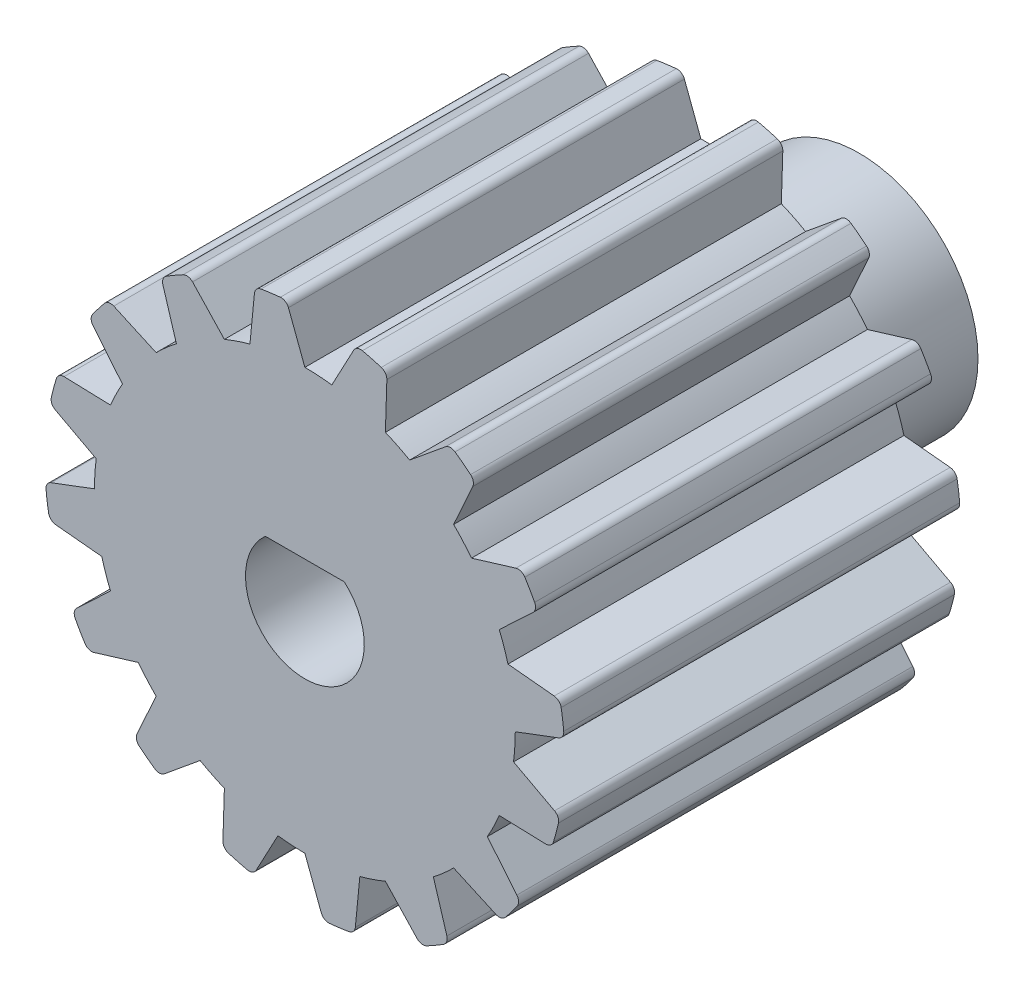
SolidWorks part; units mm, degrees
ref_plane "Alzado" through (0, 0, 0) normal (0, 0, 1) x (1, 0, 0)
ref_plane "Planta" through (0, 0, 0) normal (0, 1, 0) x (1, 0, 0)
ref_plane "Vista lateral" through (0, 0, 0) normal (1, 0, 0) x (0, 0, -1)
sketch "Croquis2" plane through (0, 0, 0) normal (0, 0, 1) x (1, 0, 0)
  line L0 (0, 0) -> (0, 7.9702) construction
  line L2 (-2.0817, 7.6936) -> (-1.9112, 9.4453)
  line L3 (-1.0408, 7.8319) -> (0, 0) construction
  line L4 (0, 7.9702) -> (-0.6221, 9.6166)
  line L5 (1.021, 7.9046) -> (1.8489, 9.4577)
  line L6 (3.0501, 7.3635) -> (3.1053, 9.1227)
  line L7 (3.9682, 6.9122) -> (5.3274, 8.0302)
  line L8 (5.6358, 5.6358) -> (6.3601, 7.2399)
  line L9 (6.3113, 4.8674) -> (7.9949, 5.3803)
  line L10 (7.3635, 3.0501) -> (8.6465, 4.2549)
  line L11 (7.6936, 2.0817) -> (9.4453, 1.9112)
  line L12 (7.9702, 0) -> (9.6166, 0.6221)
  line L13 (7.9046, -1.021) -> (9.4577, -1.8489)
  line L14 (7.3635, -3.0501) -> (9.1227, -3.1053)
  line L15 (6.9122, -3.9682) -> (8.0302, -5.3274)
  line L16 (5.6358, -5.6358) -> (7.2399, -6.3601)
  line L17 (4.8674, -6.3113) -> (5.3803, -7.9949)
  line L18 (3.0501, -7.3635) -> (4.2549, -8.6465)
  line L19 (2.0817, -7.6936) -> (1.9112, -9.4453)
  line L20 (0, -7.9702) -> (0.6221, -9.6166)
  line L21 (-1.021, -7.9046) -> (-1.8489, -9.4577)
  line L22 (-3.0501, -7.3635) -> (-3.1053, -9.1227)
  line L23 (-3.9682, -6.9122) -> (-5.3274, -8.0302)
  line L24 (-5.6358, -5.6358) -> (-6.3601, -7.2399)
  line L25 (-6.3113, -4.8674) -> (-7.9949, -5.3803)
  line L26 (-7.3635, -3.0501) -> (-8.6465, -4.2549)
  line L27 (-7.6936, -2.0817) -> (-9.4453, -1.9112)
  line L28 (-7.9702, 0) -> (-9.6166, -0.6221)
  line L29 (-7.9046, 1.021) -> (-9.4577, 1.8489)
  line L30 (-7.3635, 3.0501) -> (-9.1227, 3.1053)
  line L31 (-6.9122, 3.9682) -> (-8.0302, 5.3274)
  line L32 (-5.6358, 5.6358) -> (-7.2399, 6.3601)
  line L33 (-4.8674, 6.3113) -> (-5.3803, 7.9949)
  line L34 (-3.0501, 7.3635) -> (-4.2549, 8.6465)
  arc A0 (-4.8674, 6.3113) -> (-5.6358, 5.6358) centre (0, 0) ccw
  arc A1 (-7.5914, 6.2764) -> (-8.0413, 5.6886) centre (0, 0) ccw
  arc A2 (-1.6636, 9.7085) -> (-1.9112, 9.4453) centre (-1.6129, 9.4128) ccw
  arc A3 (-0.9298, 9.806) -> (-0.6221, 9.6166) centre (-0.9015, 9.5074) cw
  arc A4 (2.1783, 9.6061) -> (1.8489, 9.4577) centre (2.112, 9.3135) ccw
  arc A5 (2.8935, 9.4154) -> (3.1053, 9.1227) centre (2.8054, 9.1286) cw
  arc A6 (5.6886, 8.0413) -> (5.3274, 8.0302) centre (5.5153, 7.7964) ccw
  arc A7 (6.2764, 7.5914) -> (6.3601, 7.2399) centre (6.0852, 7.3602) cw
  arc A8 (8.3328, 5.2523) -> (7.9949, 5.3803) centre (8.0791, 5.0923) ccw
  arc A9 (8.7037, 4.6117) -> (8.6465, 4.2549) centre (8.4387, 4.4712) cw
  arc A10 (9.7085, 1.6636) -> (9.4453, 1.9112) centre (9.4128, 1.6129) ccw
  arc A11 (9.806, 0.9298) -> (9.6166, 0.6221) centre (9.5074, 0.9015) cw
  arc A12 (9.6061, -2.1783) -> (9.4577, -1.8489) centre (9.3135, -2.112) ccw
  arc A13 (9.4154, -2.8935) -> (9.1227, -3.1053) centre (9.1286, -2.8054) cw
  arc A14 (8.0413, -5.6886) -> (8.0302, -5.3274) centre (7.7964, -5.5153) ccw
  arc A15 (7.5914, -6.2764) -> (7.2399, -6.3601) centre (7.3602, -6.0852) cw
  arc A16 (5.2523, -8.3328) -> (5.3803, -7.9949) centre (5.0923, -8.0791) ccw
  arc A17 (4.6117, -8.7037) -> (4.2549, -8.6465) centre (4.4712, -8.4387) cw
  arc A18 (1.6636, -9.7085) -> (1.9112, -9.4453) centre (1.6129, -9.4128) ccw
  arc A19 (0.9298, -9.806) -> (0.6221, -9.6166) centre (0.9015, -9.5074) cw
  arc A20 (-2.1783, -9.6061) -> (-1.8489, -9.4577) centre (-2.112, -9.3135) ccw
  arc A21 (-2.8935, -9.4154) -> (-3.1053, -9.1227) centre (-2.8054, -9.1286) cw
  arc A22 (-5.6886, -8.0413) -> (-5.3274, -8.0302) centre (-5.5153, -7.7964) ccw
  arc A23 (-6.2764, -7.5914) -> (-6.3601, -7.2399) centre (-6.0852, -7.3602) cw
  arc A24 (-8.3328, -5.2523) -> (-7.9949, -5.3803) centre (-8.0791, -5.0923) ccw
  arc A25 (-8.7037, -4.6117) -> (-8.6465, -4.2549) centre (-8.4387, -4.4712) cw
  arc A26 (-9.7085, -1.6636) -> (-9.4453, -1.9112) centre (-9.4128, -1.6129) ccw
  arc A27 (-9.806, -0.9298) -> (-9.6166, -0.6221) centre (-9.5074, -0.9015) cw
  arc A28 (-9.6061, 2.1783) -> (-9.4577, 1.8489) centre (-9.3135, 2.112) ccw
  arc A29 (-9.4154, 2.8935) -> (-9.1227, 3.1053) centre (-9.1286, 2.8054) cw
  arc A30 (-8.0413, 5.6886) -> (-8.0302, 5.3274) centre (-7.7964, 5.5153) ccw
  arc A31 (-7.5914, 6.2764) -> (-7.2399, 6.3601) centre (-7.3602, 6.0852) cw
  arc A32 (-5.2523, 8.3328) -> (-5.3803, 7.9949) centre (-5.0923, 8.0791) ccw
  arc A33 (-4.6117, 8.7037) -> (-4.2549, 8.6465) centre (-4.4712, 8.4387) cw
  arc A34 (-4.6117, 8.7037) -> (-5.2523, 8.3328) centre (0, 0) ccw
  arc A35 (-0.9298, 9.806) -> (-1.6636, 9.7085) centre (0, 0) ccw
  arc A36 (2.8935, 9.4154) -> (2.1783, 9.6061) centre (0, 0) ccw
  arc A37 (6.2764, 7.5914) -> (5.6886, 8.0413) centre (0, 0) ccw
  arc A38 (8.7037, 4.6117) -> (8.3328, 5.2523) centre (0, 0) ccw
  arc A39 (9.4154, -2.8935) -> (9.6061, -2.1783) centre (0, 0) ccw
  arc A40 (7.5914, -6.2764) -> (8.0413, -5.6886) centre (0, 0) ccw
  arc A41 (-9.4154, 2.8935) -> (-9.6061, 2.1783) centre (0, 0) ccw
  arc A42 (-9.806, -0.9298) -> (-9.7085, -1.6636) centre (0, 0) ccw
  arc A43 (-8.7037, -4.6117) -> (-8.3328, -5.2523) centre (0, 0) ccw
  arc A44 (-6.2764, -7.5914) -> (-5.6886, -8.0413) centre (0, 0) ccw
  arc A45 (-2.8935, -9.4154) -> (-2.1783, -9.6061) centre (0, 0) ccw
  arc A46 (0.9298, -9.806) -> (1.6636, -9.7085) centre (0, 0) ccw
  arc A47 (4.6117, -8.7037) -> (5.2523, -8.3328) centre (0, 0) ccw
  arc A48 (-2.0817, 7.6936) -> (-3.0501, 7.3635) centre (0, 0) ccw
  arc A49 (1.021, 7.9046) -> (0, 7.9702) centre (0, 0) ccw
  arc A50 (3.9682, 6.9122) -> (3.0501, 7.3635) centre (0, 0) ccw
  arc A51 (6.3113, 4.8674) -> (5.6358, 5.6358) centre (0, 0) ccw
  arc A52 (7.6936, 2.0817) -> (7.3635, 3.0501) centre (0, 0) ccw
  arc A53 (7.9046, -1.021) -> (7.9702, 0) centre (0, 0) ccw
  arc A54 (9.806, 0.9298) -> (9.7085, 1.6636) centre (0, 0) ccw
  arc A55 (6.9122, -3.9682) -> (7.3635, -3.0501) centre (0, 0) ccw
  arc A56 (4.8674, -6.3113) -> (5.6358, -5.6358) centre (0, 0) ccw
  arc A57 (2.0817, -7.6936) -> (3.0501, -7.3635) centre (0, 0) ccw
  arc A58 (-1.021, -7.9046) -> (0, -7.9702) centre (0, 0) ccw
  arc A59 (-3.9682, -6.9122) -> (-3.0501, -7.3635) centre (0, 0) ccw
  arc A60 (-6.3113, -4.8674) -> (-5.6358, -5.6358) centre (0, 0) ccw
  arc A61 (-7.6936, -2.0817) -> (-7.3635, -3.0501) centre (0, 0) ccw
  arc A62 (-7.9046, 1.021) -> (-7.9702, 0) centre (0, 0) ccw
  arc A63 (-6.9122, 3.9682) -> (-7.3635, 3.0501) centre (0, 0) ccw
  dimension "D1" = 2.1
  dimension "D2" = 19.7
  dimension "D3" = 15.9404
  dimension "D6" = 0.6
  dimension "D4" = 1.76
extrude "Saliente-Extruir1" add sketch "Croquis2" along normal blind 15
sketch "Croquis3" plane through (0, 0, 15) normal (0, 0, 1) x (1, 0, 0)
  line L0 (0, 0) -> (0, 1.68) construction
  line L1 (-1.4967, 1.68) -> (1.4967, 1.68)
  arc A0 (-1.4967, 1.68) -> (1.4967, 1.68) centre (0, 0) ccw
  point P7 (0, 1.68)
  dimension "D1" = 4.5
  dimension "D2" = 1.68
sketch "Croquis5" plane through (0, 0, 0) normal (0, 0, -1) x (-1, 0, 0)
  circle A0 centre (0, 0) radius 4.5
  dimension "D1" = 9
extrude "Saliente-Extruir2" add sketch "Croquis5" along normal blind 6
extrude "Cortar-Extruir1" cut sketch "Croquis3" against normal through all
scale "Escala1" scale about origin uniform scaling yes scale factor 1.5
